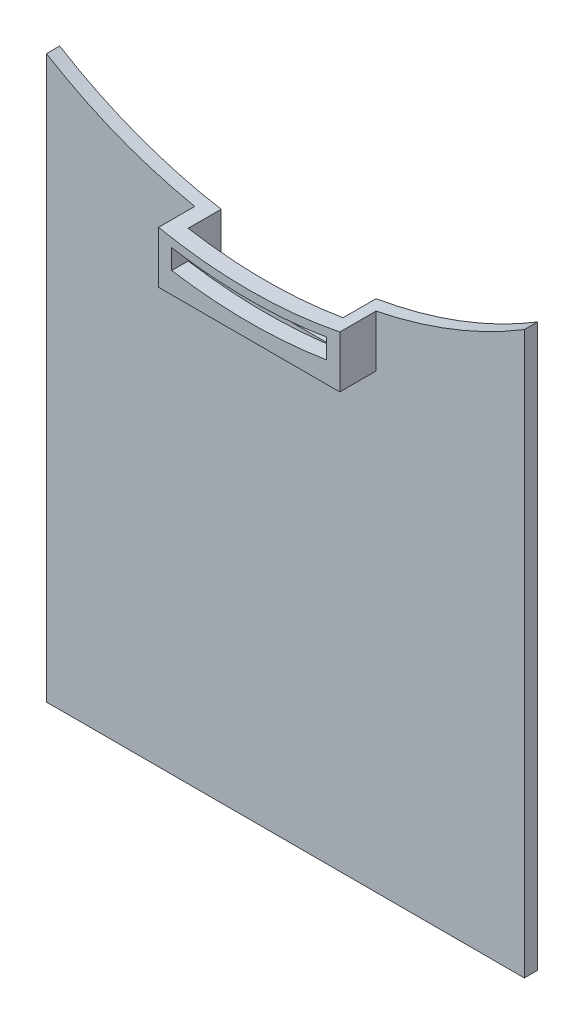
SolidWorks part; units mm, degrees
ref_plane "前视基准面" through (0, 0, 0) normal (0, 0, 1) x (1, 0, 0)
ref_plane "上视基准面" through (0, 0, 0) normal (0, 1, 0) x (1, 0, 0)
ref_plane "右视基准面" through (0, 0, 0) normal (1, 0, 0) x (0, 0, -1)
sketch " battery_upper_face" plane through (0, 0, 0) normal (0, 0, 1) x (1, 0, 0)
  line L0 (0, 8.2035) -> (0, -8.2035) construction
  line L1 (-36.25, -43.5) -> (36.25, -43.5)
  line L2 (-36.25, -43.5) -> (-36.25, 43.5)
  line L3 (-36.25, 43.5) -> (36.25, 43.5)
  line L4 (36.25, -43.5) -> (36.25, 43.5)
  line L5 (-36.25, -43.5) -> (36.25, 43.5) construction
  line L6 (-36.25, 43.5) -> (36.25, -43.5) construction
  line L7 (-11.75, 26) -> (11.75, 26) construction
  line L8 (-11.75, 25) -> (11.75, 25)
  line L9 (-11.75, 25) -> (-11.75, 43.5)
  line L10 (-11.75, 43.5) -> (11.75, 43.5)
  line L11 (11.75, 25) -> (11.75, 43.5)
  line L12 (-11.75, 25) -> (11.75, 43.5) construction
  line L13 (-11.75, 43.5) -> (11.75, 25) construction
  line L15 (-36.25, 41.6972) -> (36.25, 41.6972)
  line L16 (-36.25, 41.6972) -> (-36.25, -43.5)
  line L17 (-36.25, -43.5) -> (36.25, -43.5)
  line L18 (36.25, 41.6972) -> (36.25, -43.5)
  circle A0 centre (0, 94.5313) radius 69.5313 construction
  circle A1 centre (0, 101.0313) radius 69.5312 construction
  arc A2 (-36.25, 41.6972) -> (36.25, 41.6972) centre (0, 101.0313) ccw
  arc A3 (-11.75, 26) -> (11.75, 26) centre (0, 94.5313) ccw
  arc A4 (-11.75, 31.2) -> (11.75, 31.2) centre (0, 101.0313) ccw
  arc A5 (-11.75, 28.2) -> (11.75, 28.2) centre (0, 101.0313) ccw
  arc A6 (-11.75, 32.5) -> (69.4907, 98.6559) centre (0, 101.0313) ccw
  arc A7 (-11.75, 32.5) -> (11.75, 32.5) centre (0, 101.0313) cw
  point P0 (0, 0)
  point P7 (0, 34.25)
  point P13 (0, 0)
  dimension "D6" = 6.5
  dimension "D7" = 1.3
  dimension "D8" = 3
  dimension "D1" = 72.5
  dimension "D2" = 87
  dimension "D3" = 68.5
  dimension "D4" = 23.5
  dimension "D5" = 69.5
extrude "凸台-拉伸1" add sketch " battery_upper_face" along normal blind 2 contours A2 L2 L1 L4 L11 L8 L9 region at (0, -5.2485, 0)
extrude "凸台-拉伸6" add sketch "草图2<9>" along direction (0, 0, 1) on the side of the normal blind 7.5 contours L9 A4 L11 A2 | A5 L9 A3 L11 | A3 L8 L11 | A3 L9 L8 region at (0, 31.1898, 0) region at (0, 26.4496, 0) region at (-8.8167, 25.2996, 0) region at (8.8167, 25.2996, 0)
sketch "草图2<9>" plane through (0, 0, 0) normal (0, 0, 1) x (1, 0, 0) same geometry as " battery_upper_face"
sketch "fix_button" plane through (0, 25, 0) normal (0, -1, 0) x (1, 0, 0)
  line L0 (-11.75, 2) -> (11.75, 2) construction
  line L1 (-11.75, 5) -> (11.75, 5)
  line L2 (-11.75, 5) -> (-11.75, 0)
  line L3 (-11.75, 0) -> (11.75, 0)
  line L4 (11.75, 5) -> (11.75, 0)
  line L5 (-11.75, 5) -> (11.75, 0) construction
  line L6 (-11.75, 0) -> (11.75, 5) construction
  line L7 (-11.75, 7.5) -> (11.75, 7.5) construction
  line L8 (-13.75, 7.5) -> (13.75, 7.5)
  line L9 (-13.75, 7.5) -> (-13.75, 2)
  line L10 (-13.75, 2) -> (13.75, 2)
  line L11 (13.75, 7.5) -> (13.75, 2)
  line L12 (-13.75, 7.5) -> (13.75, 2) construction
  line L13 (-13.75, 2) -> (13.75, 7.5) construction
  line L14 (-11.75, 7.5) -> (-11.75, 2) construction
  line L15 (69.5312, 0) -> (-69.5313, 0) construction
  point P0 (0, 2.5)
  point P7 (0, 0)
  point P9 (0, 4.75)
  line M10 (-11.75, 2) -> (11.75, 2)
  line M11 (11.75, 2) -> (11.75, 7.5)
  line M13 (-11.75, 7.5) -> (-11.75, 2)
  dimension "D1" = 5
  dimension "D2" = 2
extrude "凸台-拉伸7" add sketch "fix_button" against normal up to surface (7.8731 mm away) contours L9 L10 L8 M13 | L11 L8 L10 M11 region at (-12.75, 25, 4.75) region at (12.75, 25, 4.75) up to face at (0, 35.4082, 2.875)
extrude "切除-拉伸1" cut sketch "草图4<3>" against normal blind 7.5 contours L1 M13 M10 M11 | L4 L2 L3 M10 region at (0, 25, 3.5) region at (0, 25, 1)
sketch "草图4<3>" plane through (0, 25, 0) normal (0, -1, 0) x (1, 0, 0) same geometry as "fix_button"
